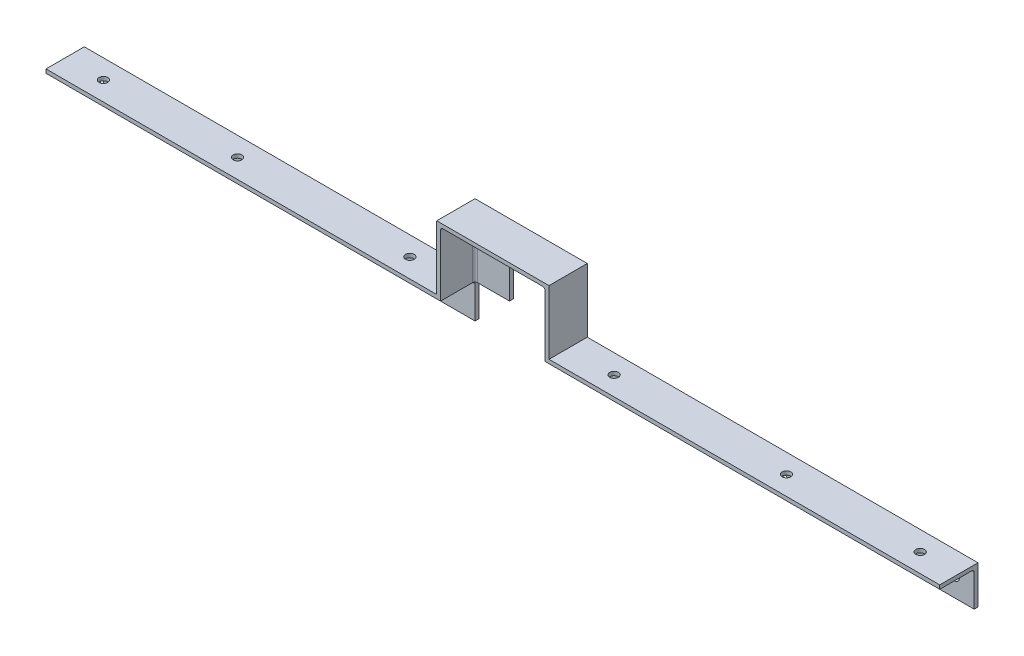
SolidWorks part; units mm, degrees
ref_plane "Plan de face" through (0, 0, 0) normal (0, 0, 1) x (1, 0, 0)
ref_plane "Plan de dessus" through (0, 0, 0) normal (0, 1, 0) x (1, 0, 0)
ref_plane "Plan de droite" through (0, 0, 0) normal (1, 0, 0) x (0, 0, -1)
ref_plane "Plan1" through (-178.4106, 149.3059, -1.5) normal (-1, 0, 0) x (0, 0, 1)
sketch "Esquisse2" plane through (0, 0, 1.5) normal (0, 0, 1) x (1, 0, 0)
  line L0 (-25.3924, 124.3059) -> (-178.4106, 124.3059)
  line L1 (-178.4106, 124.3059) -> (-178.4106, 149.3059)
  line L2 (-178.4106, 149.3059) -> (-222.3743, 149.3059)
  line L3 (-222.3743, 149.3059) -> (-222.3743, 124.3059)
  line L4 (-222.3743, 124.3059) -> (-375.3924, 124.3059)
  line L5 (-375.3924, 124.3059) -> (-375.3924, 109.3059)
  line L6 (-375.3924, 124.3059) -> (-375.3924, -75.6941) construction
  line L7 (-375.3924, 109.3059) -> (-207.3743, 109.3059)
  line L8 (-207.3743, 109.3059) -> (-207.3743, 134.3059)
  line L10 (-207.3743, 134.3059) -> (-193.4106, 134.3059)
  line L11 (-193.4106, 134.3059) -> (-193.4106, 109.3059)
  line L12 (-193.4106, 109.3059) -> (-25.3924, 109.3059)
  line L14 (-25.3924, -75.6941) -> (-25.3924, 124.3059) construction
  line L15 (-25.3924, 109.3059) -> (-25.3924, 124.3059)
  dimension "D1" = 15
  dimension "D2" = 15
  dimension "D3" = 15
  dimension "D4" = 15
extrude "Boss.-Extru.1" add sketch "Esquisse2" along normal blind 1.5
sketch "Esquisse3" plane through (0, 0, 3) normal (0, 0, 1) x (1, 0, 0)
  line L0 (-375.3924, 122.8059) -> (-220.8743, 122.8059)
  line L1 (-375.3924, 124.3059) -> (-375.3924, 109.3059) construction
  line L2 (-220.8743, 122.8059) -> (-220.8743, 147.8059)
  line L3 (-220.8743, 147.8059) -> (-179.9106, 147.8059)
  line L4 (-179.9106, 147.8059) -> (-179.9106, 122.8059)
  line L5 (-179.9106, 122.8059) -> (-25.3924, 122.8059)
  line L6 (-25.3924, 109.3059) -> (-25.3924, 124.3059) construction
  line L7 (-25.3924, 122.8059) -> (-25.3924, 124.3059)
  line L8 (-25.3924, 124.3059) -> (-178.4106, 124.3059)
  line L9 (-178.4106, 124.3059) -> (-178.4106, 149.3059)
  line L10 (-178.4106, 149.3059) -> (-222.3743, 149.3059)
  line L11 (-222.3743, 149.3059) -> (-222.3743, 124.3059)
  line L12 (-222.3743, 124.3059) -> (-375.3924, 124.3059)
  line L13 (-375.3924, 124.3059) -> (-375.3924, 122.8059)
  dimension "D1" = 1.5
  dimension "D2" = 1.5
  dimension "D3" = 1.5
  dimension "D4" = 1.5
  dimension "D5" = 1.5
extrude "Boss.-Extru.2" add sketch "Esquisse3" along normal blind 13.5
hole_wizard "Dégagement M32" positions "Esquisse3D1" profile "Esquisse6" hole size "M3" standard "ISO"
sketch3d "Esquisse3D1"
  line L0 (-375.3924, 109.3059, 3) -> (-207.3743, 109.3059, 3) construction
  line L1 (-375.3924, 122.8059, 3) -> (-375.3924, 109.3059, 3) construction
  line L3 (-193.4106, 109.3059, 3) -> (-25.3924, 109.3059, 3) construction
  line L4 (-25.3924, 109.3059, 3) -> (-25.3924, 122.8059, 3) construction
  line L6 (-179.9106, 147.8059, 3) -> (-179.9106, 122.8059, 3) construction
  line L7 (-220.8743, 122.8059, 3) -> (-220.8743, 147.8059, 3) construction
  point P0 (-229.8743, 116.8059, 3)
  point P2 (-300.3924, 116.8059, 3)
  point P4 (-367.8924, 116.8059, 3)
  point P13 (-170.9106, 116.8059, 3)
  point P15 (-100.3924, 116.8059, 3)
  point P17 (-32.8924, 116.8059, 3)
  dimension "D1" = 7.5
  dimension "D2" = 7.5
  dimension "D3" = 7.5
  dimension "D4" = 7.5
  dimension "D5" = 75
  dimension "D6" = 9
  dimension "D7" = 7.5
  dimension "D11" = 9
  dimension "D8" = 7.5
  dimension "D9" = 7.5
  dimension "D10" = 75
  dimension "D12" = 7.5
sketch "Esquisse6" plane through (-229.8743, 116.8059, 3) normal (1, 0, 0) x (0, -1, 0)
  line L0 (0, 0) -> (0, 11.0215)
  line L1 (0, 11.0215) -> (1.7, 10)
  line L2 (1.7, 10) -> (1.7, 0)
  line L5 (1.7, 0) -> (0, 0)
  line L10 (0, 11.0215) -> (-1.7, 10) construction
  line L11 (0, -6.35) -> (0, 107.95) construction
  dimension "Diamètre du perçage" = 3.4
  dimension "Profondeur du perçage" = 10
  dimension "Angle de pointe" = 118
hole_wizard "Dégagement M31" positions "Esquisse3D2" profile "Esquisse7" hole size "M3" standard "ISO"
sketch3d "Esquisse3D2"
  line L0 (-193.4106, 134.3059, 3) -> (-193.4106, 109.3059, 3) construction
  line L1 (-207.3743, 109.3059, 3) -> (-207.3743, 134.3059, 3) construction
  line L6 (-207.3743, 134.3059, 3) -> (-193.4106, 134.3059, 3) construction
  point P0 (-214.8743, 137.3059, 3)
  point P2 (-185.9106, 137.3059, 3)
  dimension "D1" = 7.5
  dimension "D2" = 7.5
  dimension "D3" = 3
  dimension "D4" = 3
sketch "Esquisse7" plane through (-214.8743, 137.3059, 3) normal (1, 0, 0) x (0, -1, 0)
  line L0 (0, 0) -> (0, 11.0215)
  line L1 (0, 11.0215) -> (1.7, 10)
  line L2 (1.7, 10) -> (1.7, 0)
  line L5 (1.7, 0) -> (0, 0)
  line L10 (0, 11.0215) -> (-1.7, 10) construction
  line L11 (0, -6.35) -> (0, 107.95) construction
  dimension "Diamètre du perçage" = 3.4
  dimension "Profondeur du perçage" = 10
  dimension "Angle de pointe" = 118
sketch "Esquisse12" plane through (0, 0, 3) normal (0, 0, 1) x (1, 0, 0)
  line L1 (-207.3743, 109.3059) -> (-220.8743, 109.3059)
  line L2 (-207.3743, 109.3059) -> (-207.3743, 122.8059)
  line L3 (-207.3743, 122.8059) -> (-220.8743, 122.8059)
  line L4 (-220.8743, 109.3059) -> (-220.8743, 122.8059)
  line L5 (-193.4106, 109.3059) -> (-179.9106, 109.3059)
  line L6 (-193.4106, 109.3059) -> (-193.4106, 122.8059)
  line L7 (-193.4106, 122.8059) -> (-179.9106, 122.8059)
  line L8 (-179.9106, 109.3059) -> (-179.9106, 122.8059)
extrude "Enlèv. mat.-Extru.1" cut sketch "Esquisse12" against normal blind 1.5
fillet "Congé1" radius 1 3 edges at (-200.3924, 147.8059, 3)
fillet "Congé2" radius 1 6 edges at (-220.8743, 147.8059, 10.25) (-220.8743, 147.513, 3.2929) (-179.9106, 147.8059, 10.25) (-179.9106, 147.513, 3.2929) (-220.8743, 134.8059, 3) (-179.9106, 134.8059, 3)
hole_wizard "Dégagement M33" positions "Esquisse3D5" profile "Esquisse15" hole size "M3" standard "ISO"
sketch3d "Esquisse3D5"
  line L0 (-179.9106, 122.8059, 16.5) -> (-25.3924, 122.8059, 16.5) construction
  line L1 (-25.3924, 124.3059, 16.5) -> (-178.4106, 124.3059, 16.5) construction
  line L2 (-222.3743, 124.3059, 16.5) -> (-375.3924, 124.3059, 16.5) construction
  line L3 (-375.3924, 124.3059, 16.5) -> (-375.3924, 124.3059, 1.5) construction
  line L4 (-25.3924, 124.3059, 16.5) -> (-25.3924, 124.3059, 1.5) construction
  point P0 (-92.8924, 124.3059, 9)
  point P2 (-40.3924, 124.3059, 9.1515)
  point P3 (-160.3924, 124.3059, 9)
  point P5 (-240.3924, 124.3059, 9)
  point P7 (-307.8924, 124.3059, 9)
  point P9 (-360.3924, 124.3059, 9)
  dimension "D1" = 7.5
  dimension "D2" = 7.5
  dimension "D3" = 7.5
  dimension "D4" = 7.5
  dimension "D5" = 7.5
  dimension "D6" = 7.5
  dimension "D7" = 15
  dimension "D8" = 67.5
  dimension "D9" = 135
  dimension "D10" = 15
  dimension "D11" = 67.5
  dimension "D12" = 135
sketch "Esquisse15" plane through (-92.8924, 124.3059, 9) normal (1, 0, 0) x (0, 0, 1)
  line L0 (0, 0) -> (0, 11.0215)
  line L1 (0, 11.0215) -> (1.7, 10)
  line L2 (1.7, 10) -> (1.7, 0)
  line L5 (1.7, 0) -> (0, 0)
  line L10 (0, 11.0215) -> (-1.7, 10) construction
  line L11 (0, -6.35) -> (0, 107.95) construction
  dimension "Diamètre du perçage" = 3.4
  dimension "Profondeur du perçage" = 10
  dimension "Angle de pointe" = 118
